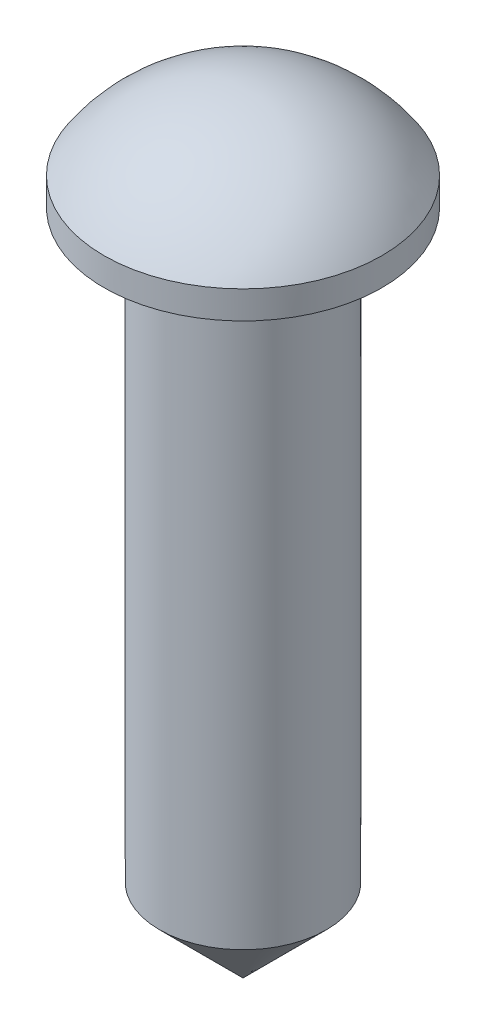
SolidWorks part; units mm, degrees
ref_plane "Front Plane" through (0, 0, 0) normal (0, 0, 1) x (1, 0, 0)
ref_plane "Top Plane" through (0, 0, 0) normal (0, 1, 0) x (1, 0, 0)
ref_plane "Right Plane" through (0, 0, 0) normal (1, 0, 0) x (0, 0, -1)
sketch "Sketch1" plane through (0, 0, 0) normal (0, 0, 1) x (1, 0, 0)
  line L2 (-1.5, -1.8417) -> (-1.5, -12.3417)
  line L3 (-1.5, -12.3417) -> (0, -13.8417)
  line L4 (0, -13.8417) -> (0, 0)
  line L5 (-2.5, -1.8417) -> (-1.5, -1.8417)
  line L6 (-2.5, -1.8417) -> (-2.5, -1.3417)
  arc A1 (-2.5, -1.3417) -> (0, 0) centre (0, -3) cw
  point P3 (-1.5, -1.2529)
  point P7 (0, 0)
  point P8 (0, 0)
  point P10 (-0.0688, 0.9059)
  point P11 (0, 0)
  point P12 (0, 0)
  point P13 (0, 0)
  point P14 (0, -0.5157)
  point P15 (0, 0)
  point P18 (0, 0)
  point P20 (0, 0)
  dimension "D4" = 0.5
  dimension "D6" = 3
  dimension "D1" = 1.5
  dimension "D2" = 45
  dimension "D3" = 12
  dimension "D5" = 1
revolve "Revolve1" add sketch "Sketch1" angle 360 about L4
